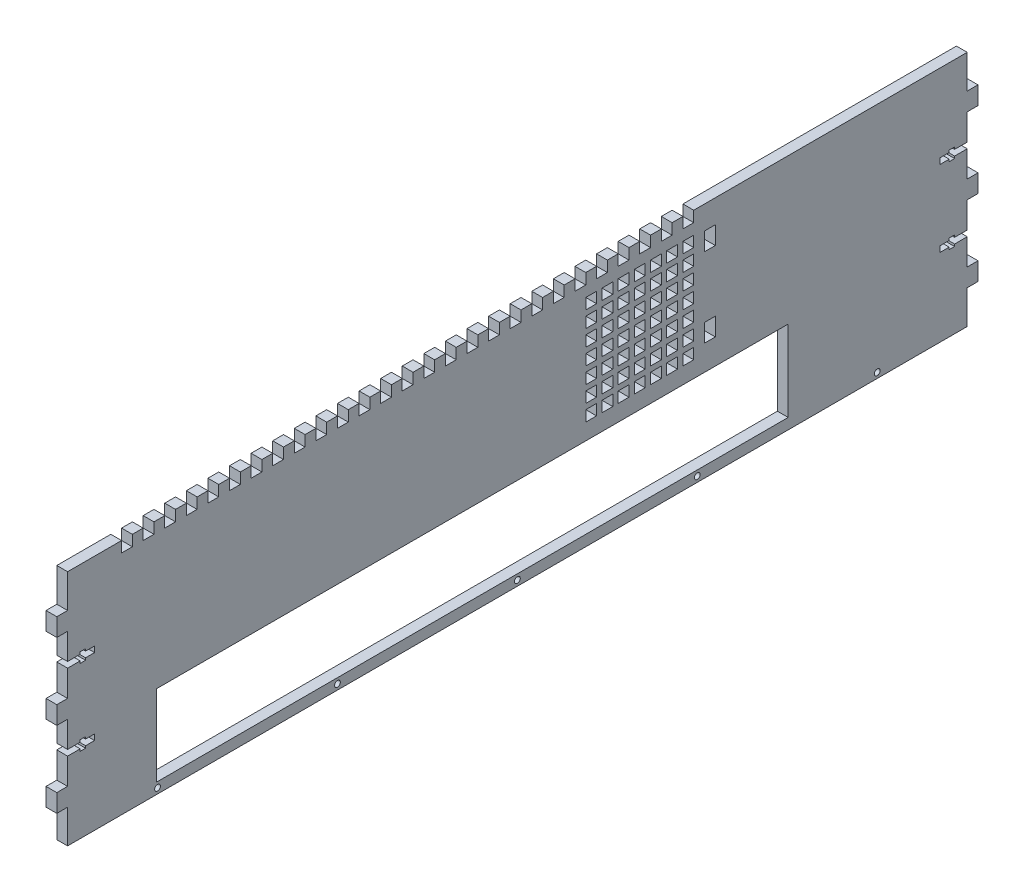
SolidWorks part; units mm, degrees
ref_plane "Front Plane" through (0, 0, 0) normal (0, 0, 1) x (1, 0, 0)
ref_plane "Top Plane" through (0, 0, 0) normal (0, 1, 0) x (1, 0, 0)
ref_plane "Right Plane" through (0, 0, 0) normal (1, 0, 0) x (0, 0, -1)
sketch "Sketch1" plane through (0, 0, 0) normal (1, 0, 0) x (0, 0, -1)
  line L1 (-250, -66) -> (250, -66)
  line L2 (-250, -66) -> (-250, 66)
  line L3 (-250, 66) -> (250, 66)
  line L4 (250, -66) -> (250, 66)
  line L5 (-250, -66) -> (250, 66) construction
  line L6 (-250, 66) -> (250, -66) construction
  point P0 (0, 0)
  dimension "D1" = 132
  dimension "D2" = 500
extrude "Boss-Extrude1" add sketch "Sketch1" along normal blind 6
sketch "Sketch3" plane through (0, 66, 0) normal (0, 1, 0) x (1, 0, 0)
  line L0 (109.75, -220) -> (6, -220) construction
  line L3 (6, -220) -> (0, -220)
  line L4 (6, -220) -> (6, -214)
  line L5 (6, -214) -> (0, -214)
  line L6 (0, -220) -> (0, -214)
  line L7 (6, -202) -> (0, -202)
  line L8 (6, -208) -> (6, -202)
  line L9 (6, -208) -> (0, -208)
  line L10 (0, -208) -> (0, -202)
  line L11 (6, -190) -> (0, -190)
  line L12 (6, -196) -> (6, -190)
  line L13 (6, -196) -> (0, -196)
  line L14 (0, -196) -> (0, -190)
  line L15 (6, -178) -> (0, -178)
  line L16 (6, -184) -> (6, -178)
  line L17 (6, -184) -> (0, -184)
  line L18 (0, -184) -> (0, -178)
  line L19 (6, -166) -> (0, -166)
  line L20 (6, -172) -> (6, -166)
  line L21 (6, -172) -> (0, -172)
  line L22 (0, -172) -> (0, -166)
  line L23 (6, -154) -> (0, -154)
  line L24 (6, -160) -> (6, -154)
  line L25 (6, -160) -> (0, -160)
  line L26 (0, -160) -> (0, -154)
  line L27 (6, -142) -> (0, -142)
  line L28 (6, -148) -> (6, -142)
  line L29 (6, -148) -> (0, -148)
  line L30 (0, -148) -> (0, -142)
  line L31 (6, -130) -> (0, -130)
  line L32 (6, -136) -> (6, -130)
  line L33 (6, -136) -> (0, -136)
  line L34 (0, -136) -> (0, -130)
  line L35 (6, -118) -> (0, -118)
  line L36 (6, -124) -> (6, -118)
  line L37 (6, -124) -> (0, -124)
  line L38 (0, -124) -> (0, -118)
  line L39 (6, -106) -> (0, -106)
  line L40 (6, -112) -> (6, -106)
  line L41 (6, -112) -> (0, -112)
  line L42 (0, -112) -> (0, -106)
  line L43 (6, -94) -> (0, -94)
  line L44 (6, -100) -> (6, -94)
  line L45 (6, -100) -> (0, -100)
  line L46 (0, -100) -> (0, -94)
  line L47 (6, -82) -> (0, -82)
  line L48 (6, -88) -> (6, -82)
  line L49 (6, -88) -> (0, -88)
  line L50 (0, -88) -> (0, -82)
  line L51 (6, -70) -> (0, -70)
  line L52 (6, -76) -> (6, -70)
  line L53 (6, -76) -> (0, -76)
  line L54 (0, -76) -> (0, -70)
  line L55 (6, -58) -> (0, -58)
  line L56 (6, -64) -> (6, -58)
  line L57 (6, -64) -> (0, -64)
  line L58 (0, -64) -> (0, -58)
  line L59 (6, -46) -> (0, -46)
  line L60 (6, -52) -> (6, -46)
  line L61 (6, -52) -> (0, -52)
  line L62 (0, -52) -> (0, -46)
  line L63 (6, -34) -> (0, -34)
  line L64 (6, -40) -> (6, -34)
  line L65 (6, -40) -> (0, -40)
  line L66 (0, -40) -> (0, -34)
  line L67 (6, -22) -> (0, -22)
  line L68 (6, -28) -> (6, -22)
  line L69 (6, -28) -> (0, -28)
  line L70 (0, -28) -> (0, -22)
  line L71 (6, -10) -> (0, -10)
  line L72 (6, -16) -> (6, -10)
  line L73 (6, -16) -> (0, -16)
  line L74 (0, -16) -> (0, -10)
  line L75 (6, 2) -> (0, 2)
  line L76 (6, -4) -> (6, 2)
  line L77 (6, -4) -> (0, -4)
  line L78 (0, -4) -> (0, 2)
  line L79 (6, 14) -> (0, 14)
  line L80 (6, 8) -> (6, 14)
  line L81 (6, 8) -> (0, 8)
  line L82 (0, 8) -> (0, 14)
  line L83 (6, 26) -> (0, 26)
  line L84 (6, 20) -> (6, 26)
  line L85 (6, 20) -> (0, 20)
  line L86 (0, 20) -> (0, 26)
  line L87 (6, 38) -> (0, 38)
  line L88 (6, 32) -> (6, 38)
  line L89 (6, 32) -> (0, 32)
  line L90 (0, 32) -> (0, 38)
  line L91 (6, 50) -> (0, 50)
  line L92 (6, 44) -> (6, 50)
  line L93 (6, 44) -> (0, 44)
  line L94 (0, 44) -> (0, 50)
  line L95 (6, 62) -> (0, 62)
  line L96 (6, 56) -> (6, 62)
  line L97 (6, 56) -> (0, 56)
  line L98 (0, 56) -> (0, 62)
  line L99 (6, 74) -> (0, 74)
  line L100 (6, 68) -> (6, 74)
  line L101 (6, 68) -> (0, 68)
  line L102 (0, 68) -> (0, 74)
  line L103 (6, 86) -> (0, 86)
  line L104 (6, 80) -> (6, 86)
  line L105 (6, 80) -> (0, 80)
  line L106 (0, 80) -> (0, 86)
  line L107 (6, 98) -> (0, 98)
  line L108 (6, 92) -> (6, 98)
  line L109 (6, 92) -> (0, 92)
  line L110 (0, 92) -> (0, 98)
  line L111 (0, 250) -> (0, -250) construction
  line L112 (6, 250) -> (6, -250) construction
  dimension "D1" = 6
  dimension "D2" = 27
extrude "Cut-Extrude2" cut sketch "Sketch3" against normal blind 6
sketch "Sketch4" plane through (0, 0, 250) normal (0, 0, 1) x (1, 0, 0)
  line L0 (0, 66) -> (0, -66) construction
  line L1 (0, 47.3321) -> (6, 47.3321)
  line L2 (0, 47.3321) -> (0, 37.3321)
  line L3 (0, 37.3321) -> (6, 37.3321)
  line L4 (6, 47.3321) -> (6, 37.3321)
  line L5 (6, 66) -> (6, -66) construction
  line L6 (0, 37.3321) -> (6, 37.3321) construction
  line L7 (0, -66) -> (0, 66) construction
  line L8 (6, 47.3321) -> (0, 47.3321) construction
  line L9 (0, -5) -> (6, -5) construction
  line L10 (0, -5) -> (6, -5)
  line L11 (0, -5) -> (0, 5)
  line L12 (0, 5) -> (6, 5)
  line L13 (6, -5) -> (6, 5)
  line L14 (6, -66) -> (6, 66) construction
  line L15 (6, 5) -> (0, 5) construction
  line L16 (6, -37.3321) -> (0, -37.3321) construction
  line L17 (0, -47.3321) -> (6, -47.3321)
  line L18 (0, -47.3321) -> (0, -37.3321)
  line L19 (0, -37.3321) -> (6, -37.3321)
  line L20 (6, -47.3321) -> (6, -37.3321)
  line L21 (0, -47.3321) -> (6, -47.3321) construction
extrude "Boss-Extrude2" add sketch "Sketch4" along normal blind 6
sketch "Sketch5" plane through (0, 0, 0) normal (-1, 0, 0) x (0, 0, 1)
  line L0 (250, 37.3321) -> (250, 5) construction
  line L1 (250, 5) -> (250, -5) construction
  line L2 (250, -5) -> (250, -37.3321) construction
  line L3 (250, 21.1661) -> (235, 21.1661) construction
  line L4 (240, -23.9661) -> (243, -18.3661) construction
  line L5 (250, 22.7661) -> (235, 22.7661)
  line L6 (240, -18.3661) -> (243, -23.9661) construction
  line L7 (250, 19.5661) -> (235, 19.5661)
  line L8 (250, -21.1661) -> (235, -21.1661) construction
  line L9 (250, 22.7661) -> (250, 19.5661)
  line L10 (235, 22.7661) -> (235, 19.5661)
  line L11 (243, -18.3661) -> (243, -23.9661)
  line L12 (240, -23.9661) -> (243, -23.9661)
  line L13 (250, 0) -> (222.8268, 0) construction
  line L14 (240, 18.3661) -> (243, 18.3661)
  line L15 (240, 18.3661) -> (240, 23.9661)
  line L16 (240, 23.9661) -> (243, 23.9661)
  line L17 (243, 18.3661) -> (243, 23.9661)
  line L18 (240, 18.3661) -> (243, 23.9661) construction
  line L19 (240, 23.9661) -> (243, 18.3661) construction
  line L20 (240, -18.3661) -> (240, -23.9661)
  line L21 (240, -18.3661) -> (243, -18.3661)
  line L22 (235, -22.7661) -> (235, -19.5661)
  line L23 (250, -22.7661) -> (250, -19.5661)
  line L24 (250, -19.5661) -> (235, -19.5661)
  line L25 (250, -22.7661) -> (235, -22.7661)
  point P20 (241.5, 21.1661)
  point P29 (241.5, -21.1661)
  dimension "D3" = 15
  dimension "D4" = 7
  dimension "D5" = 3
  dimension "D6" = 5.6
  dimension "D1" = 1.6
  dimension "D2" = 1.6
extrude "Cut-Extrude3" cut sketch "Sketch5" against normal up to next contours L17 L7 L9 L5 | L7 L17 L5 L15 | L5 L17 L16 L15 | L14 L17 L7 L15 | L7 L15 L5 L10 | L25 L23 L24 L11 | L25 L11 L24 L20 | L24 L11 L21 L20 | L11 L25 L20 L12 | L25 L20 L24 L22 region at (0, 21.1661, 246.5) region at (0, 21.1661, 241.5) region at (0, 23.3661, 241.5) region at (0, 21.1661, 237.5) region at (0, 18.9661, 241.5) region at (0, -18.9661, 241.5) region at (0, -21.1661, 246.5) region at (0, -21.1661, 241.5) region at (0, -23.3661, 241.5) region at (0, -21.1661, 237.5)
sketch "Sketch6" plane through (0, 0, -250) normal (0, 0, -1) x (-1, 0, 0)
  line L0 (0, 47.3321) -> (0, 37.3321) construction
  line L1 (0, 37.3321) -> (-6, 37.3321) construction
  line L2 (-6, 37.3321) -> (-6, 47.3321) construction
  line L3 (-6, 47.3321) -> (0, 47.3321) construction
  line L4 (0, 5) -> (0, -5) construction
  line L5 (0, -5) -> (-6, -5) construction
  line L6 (-6, -5) -> (-6, 5) construction
  line L7 (-6, 5) -> (0, 5) construction
  line L8 (0, -37.3321) -> (0, -47.3321) construction
  line L9 (0, -47.3321) -> (-6, -47.3321) construction
  line L10 (-6, -47.3321) -> (-6, -37.3321) construction
  line L11 (-6, -37.3321) -> (0, -37.3321) construction
  line L12 (0, 47.3321) -> (0, 37.3321)
  line L13 (0, 37.3321) -> (-6, 37.3321)
  line L14 (-6, 37.3321) -> (-6, 47.3321)
  line L15 (-6, 47.3321) -> (0, 47.3321)
  line L16 (0, 5) -> (0, -5)
  line L17 (0, -5) -> (-6, -5)
  line L18 (-6, -5) -> (-6, 5)
  line L19 (-6, 5) -> (0, 5)
  line L20 (0, -37.3321) -> (0, -47.3321)
  line L21 (0, -47.3321) -> (-6, -47.3321)
  line L22 (-6, -47.3321) -> (-6, -37.3321)
  line L23 (-6, -37.3321) -> (0, -37.3321)
extrude "Boss-Extrude3" add sketch "Sketch6" along normal blind 6
sketch "Sketch7" plane through (0, 0, 0) normal (-1, 0, 0) x (0, 0, 1)
  line L0 (0, 0) -> (0, -63.2146) construction
  line L1 (240, 22.7661) -> (240, 23.9661) construction
  line L2 (240, 22.7661) -> (235, 22.7661) construction
  line L3 (235, 22.7661) -> (235, 19.5661) construction
  line L4 (240, 19.5661) -> (235, 19.5661) construction
  line L5 (240, 18.3661) -> (240, 19.5661) construction
  line L6 (240, 18.3661) -> (243, 18.3661) construction
  line L7 (243, 18.3661) -> (243, 19.5661) construction
  line L8 (250, 19.5661) -> (243, 19.5661) construction
  line L9 (250, 22.7661) -> (243, 22.7661) construction
  line L10 (240, 23.9661) -> (243, 23.9661) construction
  line L11 (243, 22.7661) -> (243, 23.9661) construction
  line L12 (240, 22.7661) -> (235, 22.7661) construction
  line L13 (235, 22.7661) -> (235, 19.5661) construction
  line L14 (240, 19.5661) -> (235, 19.5661) construction
  line L15 (240, 18.3661) -> (240, 19.5661) construction
  line L16 (240, 18.3661) -> (243, 18.3661) construction
  line L17 (243, 18.3661) -> (243, 19.5661) construction
  line L18 (250, 19.5661) -> (243, 19.5661) construction
  line L19 (250, 22.7661) -> (243, 22.7661) construction
  line L20 (240, 23.9661) -> (243, 23.9661) construction
  line L21 (243, 22.7661) -> (243, 23.9661) construction
  line L22 (240, 22.7661) -> (240, 23.9661) construction
  line L23 (250, -19.5661) -> (243, -19.5661) construction
  line L24 (240, -18.3661) -> (243, -18.3661) construction
  line L25 (243, -18.3661) -> (243, -19.5661) construction
  line L26 (240, -18.3661) -> (240, -19.5661) construction
  line L27 (240, -19.5661) -> (235, -19.5661) construction
  line L28 (235, -22.7661) -> (235, -19.5661) construction
  line L29 (240, -22.7661) -> (235, -22.7661) construction
  line L30 (240, -22.7661) -> (240, -23.9661) construction
  line L31 (240, -23.9661) -> (243, -23.9661) construction
  line L32 (243, -22.7661) -> (243, -23.9661) construction
  line L33 (250, -22.7661) -> (243, -22.7661) construction
  line L34 (250, -19.5661) -> (243, -19.5661) construction
  line L35 (240, -18.3661) -> (243, -18.3661) construction
  line L36 (243, -18.3661) -> (243, -19.5661) construction
  line L37 (240, -18.3661) -> (240, -19.5661) construction
  line L38 (240, -19.5661) -> (235, -19.5661) construction
  line L39 (235, -22.7661) -> (235, -19.5661) construction
  line L40 (240, -22.7661) -> (235, -22.7661) construction
  line L41 (240, -22.7661) -> (240, -23.9661) construction
  line L42 (240, -23.9661) -> (243, -23.9661) construction
  line L43 (243, -22.7661) -> (243, -23.9661) construction
  line L44 (250, -22.7661) -> (243, -22.7661) construction
  line L45 (250, 22.7661) -> (250, 19.5661) construction
  line L46 (250, -19.5661) -> (250, -22.7661) construction
  line L47 (-250, -19.5661) -> (-250, -22.7661)
  line L48 (-250, 22.7661) -> (-250, 19.5661)
  line L49 (-250, -22.7661) -> (-243, -22.7661)
  line L50 (-243, -22.7661) -> (-243, -23.9661)
  line L51 (-240, -23.9661) -> (-243, -23.9661)
  line L52 (-240, -22.7661) -> (-240, -23.9661)
  line L53 (-240, -22.7661) -> (-235, -22.7661)
  line L54 (-235, -22.7661) -> (-235, -19.5661)
  line L55 (-240, -19.5661) -> (-235, -19.5661)
  line L56 (-240, -18.3661) -> (-240, -19.5661)
  line L57 (-243, -18.3661) -> (-243, -19.5661)
  line L58 (-240, -18.3661) -> (-243, -18.3661)
  line L59 (-250, -19.5661) -> (-243, -19.5661)
  line L60 (-240, 22.7661) -> (-240, 23.9661)
  line L61 (-243, 22.7661) -> (-243, 23.9661)
  line L62 (-240, 23.9661) -> (-243, 23.9661)
  line L63 (-250, 22.7661) -> (-243, 22.7661)
  line L64 (-250, 19.5661) -> (-243, 19.5661)
  line L65 (-243, 18.3661) -> (-243, 19.5661)
  line L66 (-240, 18.3661) -> (-243, 18.3661)
  line L67 (-240, 18.3661) -> (-240, 19.5661)
  line L68 (-240, 19.5661) -> (-235, 19.5661)
  line L69 (-235, 22.7661) -> (-235, 19.5661)
  line L70 (-240, 22.7661) -> (-235, 22.7661)
extrude "Cut-Extrude4" cut sketch "Sketch7" against normal up to next
sketch "Sketch8" plane through (0, 0, 0) normal (-1, 0, 0) x (0, 0, 1)
  line L0 (200, -15.55) -> (-150, -15.55) construction
  line L1 (200, -15.55) -> (-150, -15.55) construction
  line L2 (200, -15.55) -> (200, -60) construction
  line L3 (200, -15.55) -> (200, -60) construction
  line L186 (-150, -15.55) -> (-150, -60) construction
  line L187 (-150, -60) -> (200, -60) construction
  line L188 (200.5, -15.05) -> (200.5, -60)
  line L189 (200.5, -15.05) -> (-150.5, -15.05)
  line L190 (-150.5, -15.05) -> (-150.5, -60)
  line L191 (-150.5, -60) -> (200.5, -60)
  dimension "D1" = 0.5
extrude "Cut-Extrude5" cut sketch "Sketch8" against normal up to next
sketch "Sketch9" plane through (6, 0, 0) normal (1, 0, 0) x (0, 0, -1)
  line L0 (98, 60) -> (98, 66) construction
  line L1 (98, 54) -> (38, 54) construction
  line L2 (98, 54) -> (98, -9.05) construction
  line L3 (98, -9.05) -> (38, -9.05) construction
  line L4 (38, 54) -> (38, -9.05) construction
  line L5 (92, 60) -> (98, 60) construction
  line L6 (150.5, -15.05) -> (-200.5, -15.05) construction
  line L7 (89, 54) -> (83, 54)
  line L8 (98, 54) -> (92, 54)
  line L9 (98, 54) -> (98, 48)
  line L10 (98, 48) -> (92, 48)
  line L11 (92, 54) -> (92, 48)
  line L12 (89, 54) -> (89, 48)
  line L13 (89, 48) -> (83, 48)
  line L14 (83, 54) -> (83, 48)
  line L15 (80, 54) -> (74, 54)
  line L16 (80, 54) -> (80, 48)
  line L17 (80, 48) -> (74, 48)
  line L18 (74, 54) -> (74, 48)
  line L19 (71, 54) -> (65, 54)
  line L20 (71, 54) -> (71, 48)
  line L21 (71, 48) -> (65, 48)
  line L22 (65, 54) -> (65, 48)
  line L23 (62, 54) -> (56, 54)
  line L24 (62, 54) -> (62, 48)
  line L25 (62, 48) -> (56, 48)
  line L26 (56, 54) -> (56, 48)
  line L27 (53, 54) -> (47, 54)
  line L28 (53, 54) -> (53, 48)
  line L29 (53, 48) -> (47, 48)
  line L30 (47, 54) -> (47, 48)
  line L31 (44, 54) -> (38, 54)
  line L32 (44, 54) -> (44, 48)
  line L33 (44, 48) -> (38, 48)
  line L34 (38, 54) -> (38, 48)
  line L35 (89, 45) -> (83, 45)
  line L36 (89, 45) -> (89, 39)
  line L37 (89, 39) -> (83, 39)
  line L38 (83, 45) -> (83, 39)
  line L39 (80, 45) -> (74, 45)
  line L40 (80, 45) -> (80, 39)
  line L41 (80, 39) -> (74, 39)
  line L42 (74, 45) -> (74, 39)
  line L43 (71, 45) -> (65, 45)
  line L44 (71, 45) -> (71, 39)
  line L45 (71, 39) -> (65, 39)
  line L46 (65, 45) -> (65, 39)
  line L47 (62, 45) -> (56, 45)
  line L48 (62, 45) -> (62, 39)
  line L49 (62, 39) -> (56, 39)
  line L50 (56, 45) -> (56, 39)
  line L51 (53, 45) -> (47, 45)
  line L52 (53, 45) -> (53, 39)
  line L53 (53, 39) -> (47, 39)
  line L54 (47, 45) -> (47, 39)
  line L55 (44, 45) -> (38, 45)
  line L56 (44, 45) -> (44, 39)
  line L57 (44, 39) -> (38, 39)
  line L58 (38, 45) -> (38, 39)
  line L59 (89, 36) -> (83, 36)
  line L60 (89, 36) -> (89, 30)
  line L61 (89, 30) -> (83, 30)
  line L62 (83, 36) -> (83, 30)
  line L63 (80, 36) -> (74, 36)
  line L64 (80, 36) -> (80, 30)
  line L65 (80, 30) -> (74, 30)
  line L66 (74, 36) -> (74, 30)
  line L67 (71, 36) -> (65, 36)
  line L68 (71, 36) -> (71, 30)
  line L69 (71, 30) -> (65, 30)
  line L70 (65, 36) -> (65, 30)
  line L71 (62, 36) -> (56, 36)
  line L72 (62, 36) -> (62, 30)
  line L73 (62, 30) -> (56, 30)
  line L74 (56, 36) -> (56, 30)
  line L75 (53, 36) -> (47, 36)
  line L76 (53, 36) -> (53, 30)
  line L77 (53, 30) -> (47, 30)
  line L78 (47, 36) -> (47, 30)
  line L79 (44, 36) -> (38, 36)
  line L80 (44, 36) -> (44, 30)
  line L81 (44, 30) -> (38, 30)
  line L82 (38, 36) -> (38, 30)
  line L83 (89, 27) -> (83, 27)
  line L84 (89, 27) -> (89, 21)
  line L85 (89, 21) -> (83, 21)
  line L86 (83, 27) -> (83, 21)
  line L87 (80, 27) -> (74, 27)
  line L88 (80, 27) -> (80, 21)
  line L89 (80, 21) -> (74, 21)
  line L90 (74, 27) -> (74, 21)
  line L91 (71, 27) -> (65, 27)
  line L92 (71, 27) -> (71, 21)
  line L93 (71, 21) -> (65, 21)
  line L94 (65, 27) -> (65, 21)
  line L95 (62, 27) -> (56, 27)
  line L96 (62, 27) -> (62, 21)
  line L97 (62, 21) -> (56, 21)
  line L98 (56, 27) -> (56, 21)
  line L99 (53, 27) -> (47, 27)
  line L100 (53, 27) -> (53, 21)
  line L101 (53, 21) -> (47, 21)
  line L102 (47, 27) -> (47, 21)
  line L103 (44, 27) -> (38, 27)
  line L104 (44, 27) -> (44, 21)
  line L105 (44, 21) -> (38, 21)
  line L106 (38, 27) -> (38, 21)
  line L107 (89, 18) -> (83, 18)
  line L108 (89, 18) -> (89, 12)
  line L109 (89, 12) -> (83, 12)
  line L110 (83, 18) -> (83, 12)
  line L111 (80, 18) -> (74, 18)
  line L112 (80, 18) -> (80, 12)
  line L113 (80, 12) -> (74, 12)
  line L114 (74, 18) -> (74, 12)
  line L115 (71, 18) -> (65, 18)
  line L116 (71, 18) -> (71, 12)
  line L117 (71, 12) -> (65, 12)
  line L118 (65, 18) -> (65, 12)
  line L119 (62, 18) -> (56, 18)
  line L120 (62, 18) -> (62, 12)
  line L121 (62, 12) -> (56, 12)
  line L122 (56, 18) -> (56, 12)
  line L123 (53, 18) -> (47, 18)
  line L124 (53, 18) -> (53, 12)
  line L125 (53, 12) -> (47, 12)
  line L126 (47, 18) -> (47, 12)
  line L127 (44, 18) -> (38, 18)
  line L128 (44, 18) -> (44, 12)
  line L129 (44, 12) -> (38, 12)
  line L130 (38, 18) -> (38, 12)
  line L131 (89, 9) -> (83, 9)
  line L132 (89, 9) -> (89, 3)
  line L133 (89, 3) -> (83, 3)
  line L134 (83, 9) -> (83, 3)
  line L135 (80, 9) -> (74, 9)
  line L136 (80, 9) -> (80, 3)
  line L137 (80, 3) -> (74, 3)
  line L138 (74, 9) -> (74, 3)
  line L139 (71, 9) -> (65, 9)
  line L140 (71, 9) -> (71, 3)
  line L141 (71, 3) -> (65, 3)
  line L142 (65, 9) -> (65, 3)
  line L143 (62, 9) -> (56, 9)
  line L144 (62, 9) -> (62, 3)
  line L145 (62, 3) -> (56, 3)
  line L146 (56, 9) -> (56, 3)
  line L147 (53, 9) -> (47, 9)
  line L148 (53, 9) -> (53, 3)
  line L149 (53, 3) -> (47, 3)
  line L150 (47, 9) -> (47, 3)
  line L151 (44, 9) -> (38, 9)
  line L152 (44, 9) -> (44, 3)
  line L153 (44, 3) -> (38, 3)
  line L154 (38, 9) -> (38, 3)
  line L155 (89, 0) -> (83, 0)
  line L156 (89, 0) -> (89, -6)
  line L157 (89, -6) -> (83, -6)
  line L158 (83, 0) -> (83, -6)
  line L159 (80, 0) -> (74, 0)
  line L160 (80, 0) -> (80, -6)
  line L161 (80, -6) -> (74, -6)
  line L162 (74, 0) -> (74, -6)
  line L163 (71, 0) -> (65, 0)
  line L164 (71, 0) -> (71, -6)
  line L165 (71, -6) -> (65, -6)
  line L166 (65, 0) -> (65, -6)
  line L167 (62, 0) -> (56, 0)
  line L168 (62, 0) -> (62, -6)
  line L169 (62, -6) -> (56, -6)
  line L170 (56, 0) -> (56, -6)
  line L171 (53, 0) -> (47, 0)
  line L172 (53, 0) -> (53, -6)
  line L173 (53, -6) -> (47, -6)
  line L174 (47, 0) -> (47, -6)
  line L175 (44, 0) -> (38, 0)
  line L176 (44, 0) -> (44, -6)
  line L177 (44, -6) -> (38, -6)
  line L178 (38, 0) -> (38, -6)
  line L179 (98, 45) -> (92, 45)
  line L180 (98, 45) -> (98, 39)
  line L181 (98, 39) -> (92, 39)
  line L182 (92, 45) -> (92, 39)
  line L183 (98, 36) -> (92, 36)
  line L184 (98, 36) -> (98, 30)
  line L185 (98, 30) -> (92, 30)
  line L186 (92, 36) -> (92, 30)
  line L187 (98, 27) -> (92, 27)
  line L188 (98, 27) -> (98, 21)
  line L189 (98, 21) -> (92, 21)
  line L190 (92, 27) -> (92, 21)
  line L191 (98, 18) -> (92, 18)
  line L192 (98, 18) -> (98, 12)
  line L193 (98, 12) -> (92, 12)
  line L194 (92, 18) -> (92, 12)
  line L195 (98, 9) -> (92, 9)
  line L196 (98, 9) -> (98, 3)
  line L197 (98, 3) -> (92, 3)
  line L198 (92, 9) -> (92, 3)
  line L199 (98, 0) -> (92, 0)
  line L200 (98, 0) -> (98, -6)
  line L201 (98, -6) -> (92, -6)
  line L202 (92, 0) -> (92, -6)
  dimension "D1" = 6
  dimension "D2" = 6
  dimension "D3" = 60
  dimension "D4" = 6
  dimension "D5" = 7
  dimension "D6" = 7
extrude "Cut-Extrude6" cut sketch "Sketch9" against normal up to next (6 mm away)
sketch "Sketch10" plane through (6, 0, 0) normal (1, 0, 0) x (0, 0, -1)
  line L0 (0, 0) -> (0, -66) construction
  line L1 (-250, -66) -> (250, -66) construction
  line L2 (0, -63) -> (250, -63) construction
  line L3 (250, -66) -> (250, -47.3321) construction
  circle A0 centre (0, -63) radius 1.6
  circle A1 centre (100, -63) radius 1.6
  circle A2 centre (200, -63) radius 1.6
  circle A3 centre (-100, -63) radius 1.6
  circle A4 centre (-200, -63) radius 1.6
  dimension "D2" = 3.2
  dimension "D1" = 3
  dimension "D3" = 100
  dimension "D4" = 100
extrude "Cut-Extrude7" cut sketch "Sketch10" against normal up to next
sketch "Sketch11" plane through (6, 0, 0) normal (1, 0, 0) x (0, 0, -1)
  line L0 (110, 43) -> (110, 53) construction
  line L1 (110, 53) -> (104, 53) construction
  line L2 (104, 53) -> (104, 43) construction
  line L3 (104, 43) -> (110, 43) construction
  line L4 (110, -1) -> (110, 9) construction
  line L5 (110, 9) -> (104, 9) construction
  line L6 (104, 9) -> (104, -1) construction
  line L7 (104, -1) -> (110, -1) construction
  line L8 (110, 43) -> (110, 53)
  line L9 (110, 53) -> (104, 53)
  line L10 (104, 53) -> (104, 43)
  line L11 (104, 43) -> (110, 43)
  line L12 (110, -1) -> (110, 9)
  line L13 (110, 9) -> (104, 9)
  line L14 (104, 9) -> (104, -1)
  line L15 (104, -1) -> (110, -1)
extrude "Cut-Extrude8" cut sketch "Sketch11" against normal up to next
